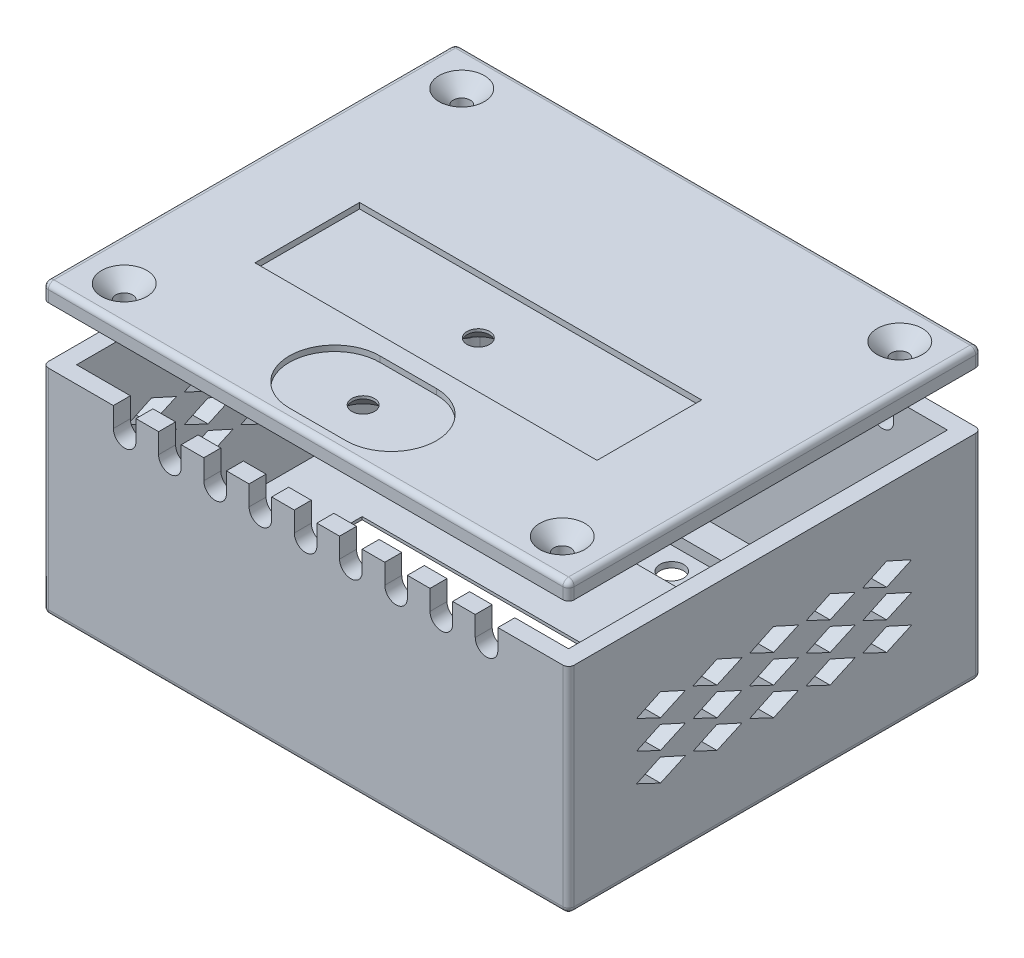
SolidWorks part; units mm, degrees
other "Крышка"
other "Корпус"
ref_plane "Спереди" through (0, 0, 0) normal (0, 0, 1) x (1, 0, 0)
ref_plane "Сверху" through (0, 0, 0) normal (0, 1, 0) x (1, 0, 0)
ref_plane "Справа" through (0, 0, 0) normal (1, 0, 0) x (0, 0, -1)
sketch "Стенки" plane through (0, 0, 0) normal (0, 1, 0) x (1, 0, 0)
  line L0 (-43.5, -33.5) -> (-43.5, 33.5)
  line L1 (-46.5, -36.5) -> (46.5, -36.5)
  line L2 (-46.5, -36.5) -> (-46.5, 36.5)
  line L3 (-46.5, 36.5) -> (46.5, 36.5)
  line L4 (46.5, -36.5) -> (46.5, 36.5)
  line L5 (-43.5, 33.5) -> (43.5, 33.5)
  line L6 (43.5, -33.5) -> (43.5, 33.5)
  line L7 (-43.5, -33.5) -> (43.5, -33.5)
  line L8 (0, 33.5) -> (0, -33.5) construction
  line L9 (43.5, 0) -> (-43.5, 0) construction
  dimension "D1" = 3
  dimension "D2" = 87
  dimension "D3" = 67
extrude "Стены" add sketch "Стенки" along normal blind 35
extrude "Дно" add sketch "Стенки<2>" against normal blind 3 contours L2 L3 L4 L1
sketch "Стенки<2>" plane through (0, 0, 0) normal (0, 1, 0) x (1, 0, 0) same geometry as "Стенки"
sketch "Экран1" plane through (0, 0, 0) normal (0, -1, 0) x (1, 0, 0)
  line L0 (-35, 32.5) -> (35, 32.5) construction
  line L6 (-35, -15.5) -> (35, -15.5) construction
  line L9 (-46.5, -36.5) -> (46.5, -36.5) construction
  line L10 (-43.5, 33.5) -> (43.5, 33.5) construction
  line L13 (-30, 27.5) -> (-30, 22.5599) construction
  line L15 (30, 27.5) -> (30, 22.5599) construction
  line L19 (0, 32.5) -> (0, -15.5) construction
  line L20 (0, -16.5) -> (0, -32.5) construction
  line L25 (-30, 27.5) -> (30, 27.5)
  line L27 (-19, -32.5) -> (19, -32.5) construction
  line L31 (-19, -32.5) -> (-19, -16.5) construction
  line L34 (-30, 17.5599) -> (-30, -11.4401) construction
  line L41 (-19, -16.5) -> (19, -16.5) construction
  line L44 (19, -32.5) -> (19, -16.5) construction
  line L45 (30, 17.5599) -> (30, -3.5) construction
  line L46 (0, 32.4078) -> (0, -15.5922) construction
  line L50 (-35, 32.5) -> (-35, -15.5) construction
  line L52 (-30, 27.5) -> (-30, -3.5)
  line L53 (-30, -3.5) -> (30, -3.5)
  line L54 (30, 27.5) -> (30, -3.5)
  line L55 (35, 32.5) -> (35, -15.5) construction
  line L56 (-19, -24.5) -> (19, -24.5) construction
  line L57 (-14, -28.5) -> (14, -28.5)
  line L58 (-14, -28.5) -> (-14, -20.5)
  line L59 (-14, -20.5) -> (14, -20.5)
  line L60 (14, -28.5) -> (14, -20.5)
  line L61 (-14, -28.5) -> (14, -20.5) construction
  line L62 (-14, -20.5) -> (14, -28.5) construction
  line L63 (-14, -24.5) -> (-6.09, -24.5) construction
  line L67 (-14, -27.0562) -> (-10.5, -27.0562) construction
  circle A4 centre (-33, 30.5) radius 1.5 construction
  circle A5 centre (31.8336, 30.5) radius 1.5 construction
  circle A6 centre (-33, -12.5) radius 1.5 construction
  circle A7 centre (33, -12.4842) radius 1.5 construction
  circle A8 centre (-16.5, -19) radius 1.25
  circle A10 centre (16.5, -19) radius 1.25
  circle A11 centre (16.5, -30) radius 1.25
  circle A12 centre (-16.5, -30) radius 1.25
  circle A13 centre (-11, -24.5) radius 2.1
  circle A15 centre (-3.75, -24.5) radius 2.1
  circle A16 centre (11, -24.5) radius 2.1
  circle A17 centre (3.75, -24.5) radius 2.1
  point P8 (0, -32.5)
  point P45 (0, -24.5)
  dimension "D7" = 3
  dimension "D10" = 2
  dimension "D11" = 2
  dimension "D9" = 2
  dimension "D13" = 43
  dimension "D15" = 2
  dimension "D18" = 42.9842
  dimension "D20" = 3
  dimension "D21" = 3
  dimension "D22" = 3
  dimension "D28" = 2.5
  dimension "D26" = 1.25
  dimension "D33" = 4.2
  dimension "D35" = 7.5
  dimension "D34" = 22
  dimension "D37" = 4.2
  dimension "D1" = 48
  dimension "D2" = 5
  dimension "D3" = 5
  dimension "D4" = 12
  dimension "D5" = 70
  dimension "D6" = 70
  dimension "D8" = 5
  dimension "D12" = 2
  dimension "D14" = 2
  dimension "D16" = 43
  dimension "D17" = 1
  dimension "D19" = 4
  dimension "D23" = 38
  dimension "D24" = 16
  dimension "D25" = 4
  dimension "D27" = 0
  dimension "D29" = 33
  dimension "D30" = 11
  dimension "D31" = 28
  dimension "D32" = 8
extrude "Вырез-экран" cut sketch "Экран1" along normal blind 3 contours L53 L54 L25 L52
sketch "Экран2" plane through (0, 0, 0) normal (0, -1, 0) x (1, 0, 0)
  line L2 (-32.75, 30.5) -> (-32.75, -12.5) construction
  line L3 (0, 32.5) -> (0, -15.5) construction
  line L4 (29.75, 30.5) -> (29.75, 35.1082)
  line L6 (-35.75, 30.5) -> (-35.75, 35.1082)
  line L7 (-35.75, 35.1082) -> (-29.75, 35.1082)
  line L8 (0, 32.5) -> (0, -15.5) construction
  line L9 (-35, 32.5) -> (35, 32.5) construction
  line L11 (-29.75, 30.5) -> (-29.75, 35.1082)
  line L12 (35.75, 35.1082) -> (29.75, 35.1082)
  line L13 (35.75, 30.5) -> (35.75, 35.1082)
  arc A4 (-35.75, 30.5) -> (-29.75, 30.5) centre (-32.75, 30.5) ccw
  circle A7 centre (-32.75, -12.5) radius 3
  circle A8 centre (-32.75, 30.5) radius 1.5
  circle A11 centre (-32.75, -12.5) radius 1.5
  circle A12 centre (32.75, -12.5) radius 1.5
  circle A14 centre (32.75, -12.5) radius 3
  circle A16 centre (32.75, 30.5) radius 1.5
  arc A17 (35.75, 30.5) -> (29.75, 30.5) centre (32.75, 30.5) cw
  dimension "D1" = 3
  dimension "D2" = 3
  dimension "D3" = 3
  dimension "D4" = 6
  dimension "D5" = 32.75
  dimension "D6" = 43
extrude "Крепление экрана" add sketch "Экран2" along normal blind 2 and the other way blind 3
chamfer "ЭКрФ" distance 2.5 distance2 3 4 edges at (0, -3, -3.5) (-30, -3, 12) (30, -3, 12) (0, -3, 27.5) first distance on face at (0, -1.5, -3.5) first distance on face at (-30, -1.5, 12) first distance on face at (30, -1.5, 12) first distance on face at (0, -1.5, 27.5)
extrude "КН1" cut sketch "Экран1<3>" along normal blind 2 contours L57 L60 L59 L58
sketch "Экран1<3>" plane through (0, 0, 0) normal (0, -1, 0) x (1, 0, 0) same geometry as "Экран1"
extrude "КН2" cut sketch "Экран1<4>" along normal through all contours A13 | A17 | A16 | A15
sketch "Экран1<4>" plane through (0, 0, 0) normal (0, -1, 0) x (1, 0, 0) same geometry as "Экран1"
extrude "КН3" add sketch "Экран1<5>" against normal blind 5 contours A11 | A10 | A8 | A12
sketch "Экран1<5>" plane through (0, 0, 0) normal (0, -1, 0) x (1, 0, 0) same geometry as "Экран1"
fillet "КН4" radius 1 4 edges at (-16.5, 5, -28.75) (-16.5, 5, -20.25) (16.5, 5, -31.25) (16.5, 5, -17.75)
sketch "Пятаки" plane through (0, 0, 0) normal (0, 1, 0) x (1, 0, 0)
  line L0 (0, 33.2786) -> (0, -33.2786) construction
  line L2 (-47.049, 0) -> (47.049, 0) construction
  line L6 (-35.485, -29.845) -> (-35.485, -34.24)
  line L9 (44.3252, -26.595) -> (44.3252, -34.24)
  line L10 (-38.735, -26.595) -> (-44.3252, -26.595)
  line L12 (-35.485, -34.24) -> (-44.3252, -34.24)
  line L13 (-44.3252, -26.595) -> (-44.3252, -34.24)
  line L14 (35.485, -34.24) -> (44.3252, -34.24)
  line L15 (38.735, -26.595) -> (44.3252, -26.595)
  line L16 (35.485, -29.845) -> (35.485, -34.24)
  line L17 (35.485, 29.845) -> (35.485, 34.24)
  line L18 (38.735, 26.595) -> (44.3252, 26.595)
  line L19 (35.485, 34.24) -> (44.3252, 34.24)
  line L20 (-44.3252, 26.595) -> (-44.3252, 34.24)
  line L21 (-35.485, 34.24) -> (-44.3252, 34.24)
  line L22 (-38.735, 26.595) -> (-44.3252, 26.595)
  line L23 (44.3252, 26.595) -> (44.3252, 34.24)
  line L24 (-35.485, 29.845) -> (-35.485, 34.24)
  arc A7 (-38.735, -26.595) -> (-35.485, -29.845) centre (-38.735, -29.845) cw
  circle A11 centre (-38.735, -29.845) radius 1.5
  circle A15 centre (38.735, -29.845) radius 1.5
  arc A16 (38.735, -26.595) -> (35.485, -29.845) centre (38.735, -29.845) ccw
  arc A19 (38.735, 26.595) -> (35.485, 29.845) centre (38.735, 29.845) cw
  circle A20 centre (38.735, 29.845) radius 1.5
  circle A21 centre (-38.735, 29.845) radius 1.5
  arc A22 (-38.735, 26.595) -> (-35.485, 29.845) centre (-38.735, 29.845) ccw
  point P3 (0, 0)
  point P8 (0, 0)
  dimension "D7" = 3
extrude "Крепление платы" add sketch "Пятаки" along normal blind 12
sketch "Решетка" plane through (-46.5, -46.5, 0) normal (1, 0, 0) x (0, -1, 0)
  line L2 (-57.7995, -14.4665) -> (-55.7995, -10.2439)
  line L9 (-57.7995, -24.4665) -> (-55.7995, -20.2439)
  line L10 (-55.7995, -20.2439) -> (-57.7995, -15.8355)
  line L11 (-57.7995, -15.8355) -> (-59.7995, -20.2439)
  line L12 (-59.7995, -20.2439) -> (-57.7995, -24.4665)
  line L13 (-62.7995, -24.4665) -> (-60.7995, -20.2439)
  line L14 (-60.7995, -20.2439) -> (-62.7995, -15.8355)
  line L15 (-62.7995, -15.8355) -> (-64.7995, -20.2439)
  line L16 (-64.7995, -20.2439) -> (-62.7995, -24.4665)
  line L17 (-67.7995, -24.4665) -> (-65.7995, -20.2439)
  line L18 (-65.7995, -20.2439) -> (-67.7995, -15.8355)
  line L19 (-67.7995, -15.8355) -> (-69.7995, -20.2439)
  line L20 (-69.7995, -20.2439) -> (-67.7995, -24.4665)
  line L89 (-55.7995, -10.2439) -> (-57.7995, -5.8355)
  line L90 (-57.7995, -5.8355) -> (-59.7995, -10.2439)
  line L91 (-59.7995, -10.2439) -> (-57.7995, -14.4665)
  line L92 (-62.7995, -14.4665) -> (-60.7995, -10.2439)
  line L221 (-60.7995, -10.2439) -> (-62.7995, -5.8355)
  line L222 (-62.7995, -5.8355) -> (-64.7995, -10.2439)
  line L223 (-64.7995, -10.2439) -> (-62.7995, -14.4665)
  line L224 (-67.7995, -14.4665) -> (-65.7995, -10.2439)
  line L229 (-65.7995, -10.2439) -> (-67.7995, -5.8355)
  line L230 (-67.7995, -5.8355) -> (-69.7995, -10.2439)
  line L231 (-69.7995, -10.2439) -> (-67.7995, -14.4665)
  line L232 (-57.7995, -4.4665) -> (-55.7995, -0.2439)
  line L233 (-55.7995, -0.2439) -> (-57.7995, 4.1645)
  line L234 (-57.7995, 4.1645) -> (-59.7995, -0.2439)
  line L235 (-59.7995, -0.2439) -> (-57.7995, -4.4665)
  line L236 (-62.7995, -4.4665) -> (-60.7995, -0.2439)
  line L237 (-60.7995, -0.2439) -> (-62.7995, 4.1645)
  line L238 (-62.7995, 4.1645) -> (-64.7995, -0.2439)
  line L239 (-64.7995, -0.2439) -> (-62.7995, -4.4665)
  line L240 (-67.7995, -4.4665) -> (-65.7995, -0.2439)
  line L241 (-65.7995, -0.2439) -> (-67.7995, 4.1645)
  line L242 (-67.7995, 4.1645) -> (-69.7995, -0.2439)
  line L243 (-69.7995, -0.2439) -> (-67.7995, -4.4665)
  line L244 (-57.7995, 5.5335) -> (-55.7995, 9.7561)
  line L245 (-55.7995, 9.7561) -> (-57.7995, 14.1645)
  line L246 (-57.7995, 14.1645) -> (-59.7995, 9.7561)
  line L247 (-59.7995, 9.7561) -> (-57.7995, 5.5335)
  line L248 (-62.7995, 5.5335) -> (-60.7995, 9.7561)
  line L249 (-60.7995, 9.7561) -> (-62.7995, 14.1645)
  line L250 (-62.7995, 14.1645) -> (-64.7995, 9.7561)
  line L251 (-64.7995, 9.7561) -> (-62.7995, 5.5335)
  line L252 (-67.7995, 5.5335) -> (-65.7995, 9.7561)
  line L253 (-65.7995, 9.7561) -> (-67.7995, 14.1645)
  line L254 (-67.7995, 14.1645) -> (-69.7995, 9.7561)
  line L255 (-69.7995, 9.7561) -> (-67.7995, 5.5335)
  line L256 (-57.7995, 15.5335) -> (-55.7995, 19.7561)
  line L257 (-55.7995, 19.7561) -> (-57.7995, 24.1645)
  line L258 (-57.7995, 24.1645) -> (-59.7995, 19.7561)
  line L259 (-59.7995, 19.7561) -> (-57.7995, 15.5335)
  line L260 (-62.7995, 15.5335) -> (-60.7995, 19.7561)
  line L261 (-60.7995, 19.7561) -> (-62.7995, 24.1645)
  line L262 (-62.7995, 24.1645) -> (-64.7995, 19.7561)
  line L263 (-64.7995, 19.7561) -> (-62.7995, 15.5335)
  line L264 (-67.7995, 15.5335) -> (-65.7995, 19.7561)
  line L265 (-65.7995, 19.7561) -> (-67.7995, 24.1645)
  line L266 (-67.7995, 24.1645) -> (-69.7995, 19.7561)
  line L267 (-69.7995, 19.7561) -> (-67.7995, 15.5335)
  dimension "D1" = 5
extrude "Вентиляция" cut sketch "Решетка" along normal through all
sketch "Эскиз6" plane through (0, 0, -36.5) normal (0, 0, -1) x (-1, 0, 0)
  line L0 (0, 35) -> (0, 0) construction
  line L1 (-46.5, 35) -> (46.5, 35) construction
  line L38 (2, 31.4807) -> (2, 35)
  line L39 (2, 35) -> (-2, 35)
  line L40 (-2, 35) -> (-2, 31.4807)
  line L52 (10, 31.4807) -> (10, 35)
  line L59 (10, 35) -> (6, 35)
  line L60 (6, 35) -> (6, 31.4807)
  line L61 (18, 31.4807) -> (18, 35)
  line L62 (18, 35) -> (14, 35)
  line L63 (14, 35) -> (14, 31.4807)
  line L64 (26, 31.4807) -> (26, 35)
  line L65 (26, 35) -> (22, 35)
  line L66 (22, 35) -> (22, 31.4807)
  line L67 (34, 31.4807) -> (34, 35)
  line L68 (34, 35) -> (30, 35)
  line L69 (30, 35) -> (30, 31.4807)
  line L70 (-6, 31.4807) -> (-6, 35)
  line L71 (-6, 35) -> (-10, 35)
  line L72 (-10, 35) -> (-10, 31.4807)
  line L73 (-14, 31.4807) -> (-14, 35)
  line L74 (-14, 35) -> (-18, 35)
  line L75 (-18, 35) -> (-18, 31.4807)
  line L76 (-22, 31.4807) -> (-22, 35)
  line L77 (-22, 35) -> (-26, 35)
  line L78 (-26, 35) -> (-26, 31.4807)
  line L79 (-30, 31.4807) -> (-30, 35)
  line L80 (-30, 35) -> (-34, 35)
  line L81 (-34, 35) -> (-34, 31.4807)
  arc A12 (-2, 31.4807) -> (2, 31.4807) centre (0, 31.4807) ccw
  arc A18 (6, 31.4807) -> (10, 31.4807) centre (8, 31.4807) ccw
  arc A19 (14, 31.4807) -> (18, 31.4807) centre (16, 31.4807) ccw
  arc A20 (22, 31.4807) -> (26, 31.4807) centre (24, 31.4807) ccw
  arc A21 (30, 31.4807) -> (34, 31.4807) centre (32, 31.4807) ccw
  arc A22 (-10, 31.4807) -> (-6, 31.4807) centre (-8, 31.4807) ccw
  arc A23 (-18, 31.4807) -> (-14, 31.4807) centre (-16, 31.4807) ccw
  arc A24 (-26, 31.4807) -> (-22, 31.4807) centre (-24, 31.4807) ccw
  arc A25 (-34, 31.4807) -> (-30, 31.4807) centre (-32, 31.4807) ccw
  dimension "D1" = 5
  dimension "D2" = 5
extrude "Кабельканалы" cut sketch "Эскиз6" against normal through all
ref_plane "Плоскость1" through (0, 45, 0) normal (0, 1, 0) x (1, 0, 0)
sketch "Эскиз7" plane through (0, 45, 0) normal (0, 1, 0) x (1, 0, 0)
  line L0 (-43, -33) -> (-43, 33)
  line L1 (-46.5, -36.5) -> (46.5, -36.5)
  line L2 (-46.5, -36.5) -> (-46.5, 36.5)
  line L3 (-46.5, 36.5) -> (46.5, 36.5)
  line L4 (46.5, -36.5) -> (46.5, 36.5)
  line L5 (-43, 33) -> (43, 33)
  line L6 (43, -33) -> (43, 33)
  line L7 (-43, -33) -> (43, -33)
  circle A0 centre (-38.735, 29.845) radius 1.5
  circle A1 centre (38.735, 29.845) radius 1.5
  circle A2 centre (38.735, -29.845) radius 1.5
  circle A3 centre (-38.735, -29.845) radius 1.5
  dimension "D1" = 3.5
fillet "Скругление2" radius 1 8 edges at (-46.5, 16, 36.5) (-46.5, 16, -36.5) (46.5, 16, -36.5) (46.5, 16, 36.5) (46.5, -3, 0) (0, -3, 36.5) (-46.5, -3, 0) (0, -3, -36.5)
extrude "Верхняя крышка" add sketch "Эскиз7" along normal blind 3 separate body contours L2 L3 L4 L1 | A0 | A1 | A2 | A3
extrude "Верхняя крышка 2" add sketch "Эскиз7<3>" against normal blind 1 contours L0 L5 L6 L7 | A1 | A2 | A3 | A0
sketch "Эскиз7<3>" plane through (0, 45, 0) normal (0, 1, 0) x (1, 0, 0) same geometry as "Эскиз7"
fillet "Скругление3" radius 1 8 edges at (-46.5, 46.5, 36.5) (46.5, 46.5, 36.5) (46.5, 46.5, -36.5) (-46.5, 46.5, -36.5) (-46.5, 48, 0) (0, 48, 36.5) (46.5, 48, 0) (0, 48, -36.5)
chamfer "Фаска2" distance 2.5 angle 45 4 edges at (38.735, 48, -28.345) (-38.735, 48, -28.345) (-38.735, 48, 31.345) (38.735, 48, 31.345)
sketch "Эскиз4" plane through (0, 48, 0) normal (0, 1, 0) x (-1, 0, 0)
  line L0 (0.049, 24.3196) -> (0.049, 28.3184) construction
  line L1 (5.049, 18.319) -> (-4.951, 18.319)
  line L2 (5.049, 34.319) -> (-4.951, 34.319)
  line L4 (-2, 26.319) -> (2, 26.319) construction
  line L6 (-30.1646, 15.1236) -> (30.3354, 15.1236)
  line L7 (-30.1646, 15.1236) -> (-30.1646, -3.3764)
  line L8 (-30.1646, -3.3764) -> (30.3354, -3.3764)
  line L9 (30.3354, 15.1236) -> (30.3354, -3.3764)
  line L10 (-30.1646, 15.1236) -> (30.3354, -3.3764) construction
  line L11 (-30.1646, -3.3764) -> (30.3354, 15.1236) construction
  circle A0 centre (0, 26.319) radius 2
  arc A1 (5.049, 18.319) -> (5.049, 34.319) centre (5.049, 26.319) ccw
  arc A2 (-4.951, 34.319) -> (-4.951, 18.319) centre (-4.951, 26.319) ccw
  circle A3 centre (0.0854, 5.8736) radius 2
  point P2 (0.0854, 5.8736)
  dimension "D1" = 60.5
  dimension "D2" = 18.5
extrude "Крепеж1" cut sketch "Эскиз4" against normal blind 1 contours A2 L1 A1 L2 | L6 L9 L8 L7
extrude "Крепеж2" cut sketch "Эскиз4<3>" against normal blind 5 contours A3 | A0
sketch "Эскиз4<3>" plane through (0, 48, 0) normal (0, 1, 0) x (-1, 0, 0) same geometry as "Эскиз4"
chamfer "Фаска3" distance 2.5 angle 45 2 edges at (-0.0854, 44, 7.8736) (0, 44, 28.319)
sketch "Эскиз8" plane through (0, -3, 0) normal (0, -1, 0) x (1, 0, 0)
  line L30 (0, -35.5) -> (0, -6.5) construction
  line L31 (-45.5, -35.5) -> (45.5, -35.5) construction
  line L32 (33, -6.5) -> (-33, -6.5) construction
  line L33 (-12.0617, -14.588) -> (-9.8637, -14.588)
  line L34 (-9.8637, -14.588) -> (-9.8637, -15.6464)
  line L35 (-9.8637, -15.6464) -> (-12.0617, -15.6464)
  line L36 (-12.0617, -15.6464) -> (-12.0617, -14.588)
  line L37 (-4.572, -13.8554) -> (-4.572, -12.3086)
  line L38 (-4.572, -12.3086) -> (-3.5137, -12.3086)
  line L39 (-3.5137, -12.3086) -> (-3.5137, -13.8554)
  line L40 (-3.5137, -13.8554) -> (-1.8854, -13.8554)
  line L41 (-1.8854, -13.8554) -> (-1.8854, -14.9137)
  line L42 (-1.8854, -14.9137) -> (-3.5137, -14.9137)
  line L43 (-3.5137, -14.9137) -> (-3.5137, -16.4605)
  line L44 (-3.5137, -16.4605) -> (-4.572, -16.4605)
  line L45 (-4.572, -16.4605) -> (-4.572, -14.9137)
  line L46 (-4.572, -14.9137) -> (-6.2002, -14.9137)
  line L47 (-6.2002, -14.9137) -> (-6.2002, -13.8554)
  line L48 (-6.2002, -13.8554) -> (-4.572, -13.8554)
  line L49 (1.778, -11.0874) -> (5.1972, -11.0874)
  line L50 (5.1972, -11.0874) -> (5.1972, -12.2271)
  line L51 (5.1972, -12.2271) -> (2.9178, -12.2271)
  line L52 (2.9178, -12.2271) -> (2.9178, -13.4483)
  line L53 (2.9178, -13.4483) -> (5.1972, -13.4483)
  line L54 (5.1972, -13.4483) -> (5.1972, -14.588)
  line L55 (5.1972, -14.588) -> (2.9178, -14.588)
  line L56 (2.9178, -14.588) -> (2.9178, -16.2977)
  line L57 (2.9178, -16.2977) -> (5.1972, -16.2977)
  line L58 (5.1972, -16.2977) -> (5.1972, -17.4374)
  line L59 (5.1972, -17.4374) -> (1.778, -17.4374)
  line L60 (1.778, -17.4374) -> (1.778, -11.0874)
  line L61 (12.0357, -11.9359) -> (11.1834, -12.7156)
  line L62 (8.2908, -16.2481) -> (9.2932, -15.6464)
  spline S0 degree 3 poles (11.1834, -12.7156) (11.1152, -12.6156) (11.0081, -12.4774) (10.8501, -12.3199) (10.7365, -12.2269) (10.6213, -12.1545) (10.4693, -12.087) (10.349, -12.0641) (10.2701, -12.0643) knots 0 0 0 0 0.311824 0.448433 0.573381 0.689077 0.797573 1 1 1 1
  spline S1 degree 3 poles (10.2701, -12.0643) (10.2008, -12.0642) (10.0974, -12.0766) (9.9761, -12.1344) (9.899, -12.1893) (9.8379, -12.2555) (9.7738, -12.3464) (9.7568, -12.428) (9.7562, -12.4803) knots 0 0 0 0 0.285993 0.416634 0.54738 0.671583 0.784401 1 1 1 1
  spline S2 degree 3 poles (9.7562, -12.4803) (9.7554, -12.5336) (9.7757, -12.6424) (9.8286, -12.7393) (9.8618, -12.7843) knots 0 0 0 0 0.487115 1 1 1 1
  spline S3 degree 3 poles (9.8618, -12.7843) (9.8943, -12.8277) (9.9575, -12.8957) (10.0547, -12.9947) (10.1546, -13.0894) (10.2699, -13.1997) (10.4623, -13.372) (10.6153, -13.5086) (10.7242, -13.6035) knots 0 0 0 0 0.136349 0.233805 0.349411 0.483179 0.635967 1 1 1 1
  spline S4 degree 3 poles (10.7242, -13.6035) (10.8253, -13.6915) (10.9703, -13.8152) (11.15, -13.974) (11.2611, -14.0719) (11.3549, -14.1566) (11.4472, -14.2428) (11.5078, -14.301) (11.5422, -14.3362) knots 0 0 0 0 0.366184 0.520457 0.655012 0.770624 0.865677 1 1 1 1
  spline S5 degree 3 poles (11.5422, -14.3362) (11.6516, -14.451) (11.801, -14.6249) (11.9613, -14.8707) (12.0505, -15.0461) (12.1178, -15.2231) (12.1822, -15.4698) (12.1987, -15.6627) (12.1985, -15.7927) knots 0 0 0 0 0.289954 0.417139 0.535255 0.648751 0.762405 1 1 1 1
  spline S6 degree 3 poles (12.1985, -15.7927) (12.2006, -15.9186) (12.1821, -16.1041) (12.1288, -16.343) (12.0687, -16.5094) (11.9953, -16.6687) (11.9033, -16.8184) (11.7952, -16.9601) (11.6713, -17.0911) (11.5343, -17.2101) (11.3874, -17.3159) (11.2291, -17.4033) (11.0607, -17.4753) (10.8824, -17.5307) (10.6267, -17.5867) (10.427, -17.6005) (10.2917, -17.6002) knots 0 0 0 0 0.127927 0.189047 0.248544 0.307607 0.367248 0.426963 0.488617 0.550392 0.611331 0.672556 0.734024 0.797341 0.86225 1 1 1 1
  spline S7 degree 3 poles (10.2917, -17.6002) (10.1842, -17.6001) (10.025, -17.5907) (9.8183, -17.5566) (9.6708, -17.5206) (9.5283, -17.4749) (9.3908, -17.4192) (9.2591, -17.3524) (9.1324, -17.276) (9.0112, -17.1874) (8.894, -17.0882) (8.7819, -16.977) (8.6744, -16.8541) (8.5723, -16.7191) (8.4357, -16.5212) (8.348, -16.3593) (8.2908, -16.2481) knots 0 0 0 0 0.125868 0.18624 0.244977 0.303358 0.36123 0.418489 0.475937 0.534204 0.594059 0.655469 0.718772 0.784975 0.853522 1 1 1 1
  spline S8 degree 3 poles (9.2932, -15.6464) (9.3615, -15.7711) (9.4725, -15.9437) (9.6446, -16.1416) (9.7735, -16.2573) (9.9067, -16.348) (10.0888, -16.4341) (10.2363, -16.4607) (10.3337, -16.4605) knots 0 0 0 0 0.307612 0.442139 0.566229 0.681222 0.789558 1 1 1 1
  spline S9 degree 3 poles (10.3337, -16.4605) (10.4295, -16.4612) (10.5706, -16.4395) (10.7414, -16.3625) (10.8499, -16.2823) (10.9415, -16.1897) (11.0314, -16.0541) (11.0601, -15.9363) (11.0588, -15.8588) knots 0 0 0 0 0.275473 0.404346 0.53543 0.661427 0.777867 1 1 1 1
  spline S10 degree 3 poles (11.0588, -15.8588) (11.0586, -15.785) (11.0364, -15.6726) (10.9722, -15.5301) (10.9144, -15.4404) (10.8555, -15.3653) (10.7992, -15.3002) (10.7306, -15.2283) (10.65, -15.1494) (10.5583, -15.063) (10.4145, -14.9314) (10.2982, -14.8321) (10.2167, -14.7636) knots 0 0 0 0 0.155091 0.238352 0.328404 0.379384 0.439618 0.509831 0.588875 0.677436 0.775547 1 1 1 1
  spline S11 degree 3 poles (10.2167, -14.7636) (10.061, -14.633) (9.8395, -14.4417) (9.564, -14.1889) (9.3899, -14.0182) (9.2369, -13.861) (9.1061, -13.7162) (8.999, -13.5826) (8.8862, -13.4243) (8.7793, -13.2314) (8.6574, -12.9282) (8.6148, -12.6911) (8.6165, -12.535) knots 0 0 0 0 0.215201 0.309902 0.395959 0.473447 0.54214 0.602523 0.654726 0.747804 0.835278 1 1 1 1
  spline S12 degree 3 poles (8.6165, -12.535) (8.6159, -12.4278) (8.6319, -12.2689) (8.681, -12.0641) (8.7335, -11.9182) (8.8017, -11.7786) (8.8845, -11.6445) (8.9832, -11.5173) (9.0945, -11.397) (9.217, -11.287) (9.348, -11.19) (9.4867, -11.108) (9.6322, -11.04) (9.7854, -10.988) (10.0015, -10.9378) (10.1696, -10.9253) (10.2828, -10.9246) knots 0 0 0 0 0.124457 0.184841 0.244567 0.304319 0.3652 0.427421 0.491262 0.555499 0.618605 0.680495 0.742473 0.804991 0.868252 1 1 1 1
  spline S13 degree 3 poles (10.2828, -10.9246) (10.4319, -10.9247) (10.6555, -10.9526) (10.9423, -11.0426) (11.1158, -11.1233) (11.2538, -11.2017) (11.3595, -11.2738) (11.4672, -11.3565) (11.5775, -11.4499) (11.6885, -11.5558) (11.8462, -11.7148) (11.9605, -11.8444) (12.0357, -11.9359) knots 0 0 0 0 0.212977 0.319777 0.428556 0.485857 0.546559 0.611431 0.679821 0.753159 0.830753 1 1 1 1
extrude "Надпись" cut sketch "Эскиз8" against normal blind 1
